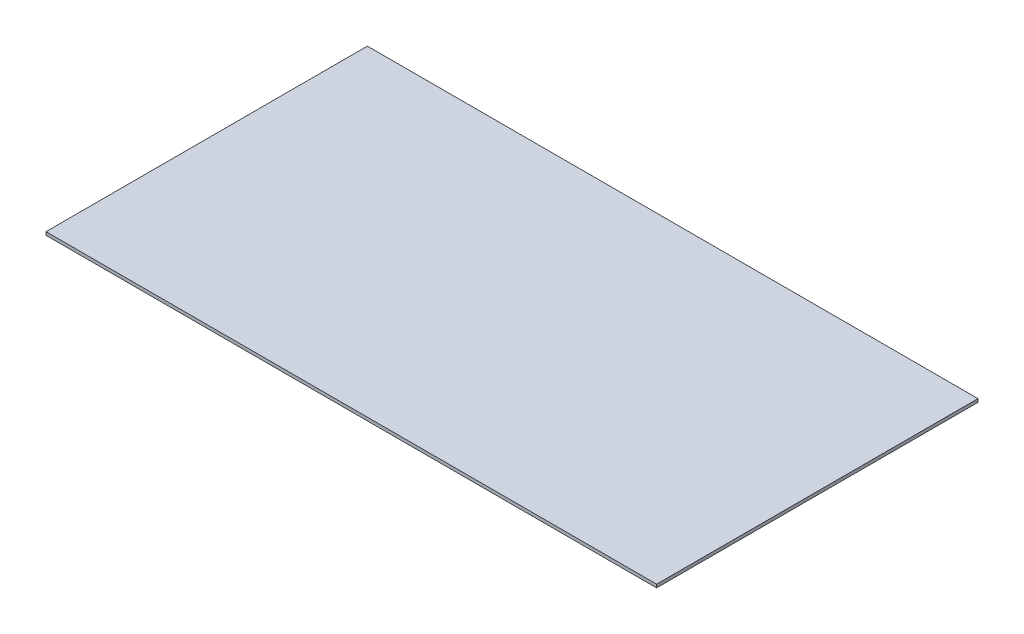
SolidWorks part; units mm, degrees
material "Balsa"
ref_plane "Front Plane" through (0, 0, 0) normal (0, 0, 1) x (1, 0, 0)
ref_plane "Top Plane" through (0, 0, 0) normal (0, 1, 0) x (1, 0, 0)
ref_plane "Right Plane" through (0, 0, 0) normal (1, 0, 0) x (0, 0, -1)
sketch "Sketch1" plane through (0, 0, 0) normal (0, 1, 0) x (1, 0, 0)
  line L1 (-241.3, -127) -> (241.3, -127)
  line L2 (-241.3, -127) -> (-241.3, 127)
  line L3 (-241.3, 127) -> (241.3, 127)
  line L4 (241.3, -127) -> (241.3, 127)
  line L5 (-241.3, -127) -> (241.3, 127) construction
  line L6 (-241.3, 127) -> (241.3, -127) construction
  point P0 (0, 0)
  dimension "D1" = 254
  dimension "D2" = 482.6
extrude "Work Area 19x10in" add sketch "Sketch1" along normal blind 2.54
